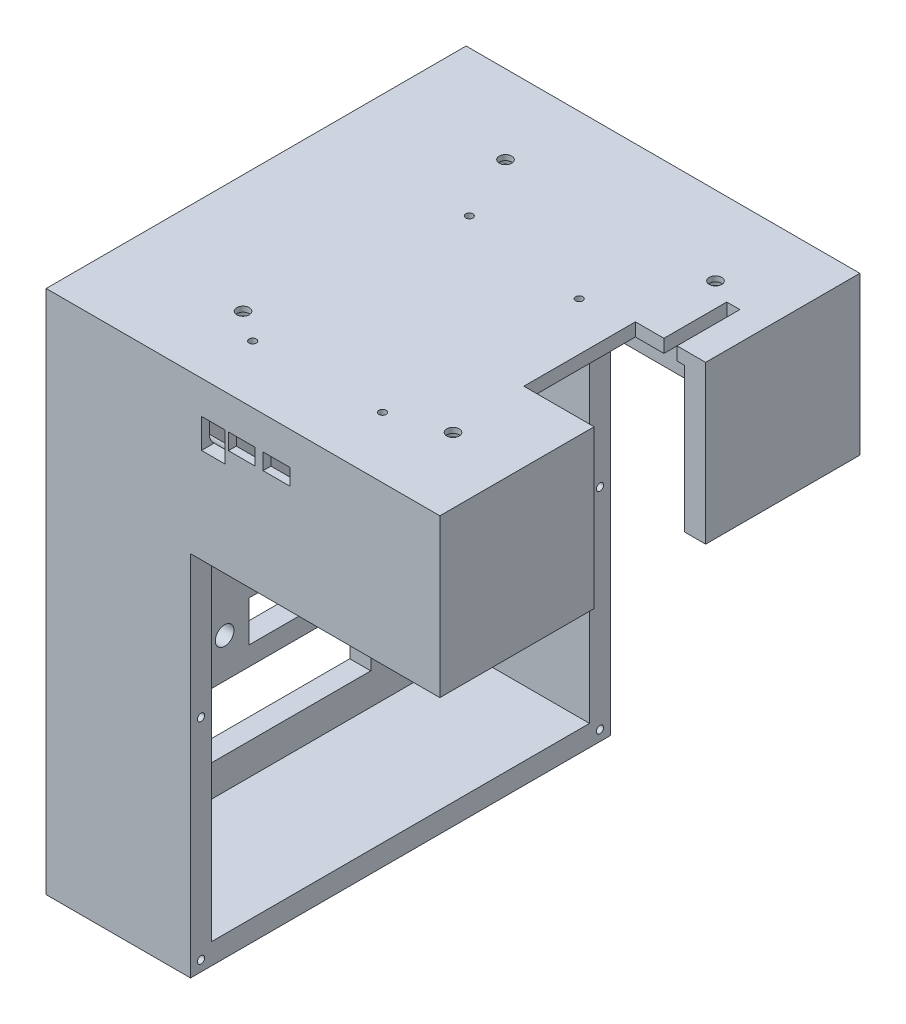
SolidWorks part; units mm, degrees
ref_plane "Front" through (0, 0, 0) normal (0, 0, 1) x (1, 0, 0)
ref_plane "Top" through (0, 0, 0) normal (0, 1, 0) x (1, 0, 0)
ref_plane "Right" through (0, 0, 0) normal (1, 0, 0) x (0, 0, -1)
sketch "Sketch1" plane through (0, 0, 0) normal (0, 1, 0) x (1, 0, 0)
  line L1 (-75, -80) -> (75, -80)
  line L2 (-75, -80) -> (-75, 80)
  line L3 (-75, 80) -> (75, 80)
  line L4 (75, -80) -> (75, 80)
  line L5 (-75, -80) -> (75, 80) construction
  line L6 (-75, 80) -> (75, -80) construction
  point P0 (0, 0)
  dimension "L" = 150
  dimension "W" = 160
extrude "Boss-Extrude1" add sketch "Sketch1" along normal blind 50 and the other way blind 10
sketch "Sketch3" plane through (0, 0, 0) normal (0, 1, 0) x (1, 0, 0)
  line L0 (-75, 80) -> (-75, -80) construction
  line L1 (-67, -72) -> (67, -72)
  line L2 (-67, -72) -> (-67, 72)
  line L3 (-67, 72) -> (67, 72)
  line L4 (67, -72) -> (67, 72)
  line L5 (-67, -72) -> (67, 72) construction
  line L6 (-67, 72) -> (67, -72) construction
  line L7 (75, 80) -> (-75, 80) construction
  point P0 (0, 0)
  dimension "D1" = 8
  dimension "D2" = 8
extrude "Cut-Extrude1" cut sketch "Sketch3" along normal blind 45 and the other way blind 10
ref_plane "Plane1" through (-75, 0, 0) normal (-1, 0, 0) x (0, 0, 1)
sketch "Sketch4" plane through (-75, 0, 0) normal (-1, 0, 0) x (0, 0, 1)
  line L0 (80, 50) -> (80, -10) construction
  line L1 (-80, -10) -> (80, -10)
  line L2 (-80, -10) -> (-80, -150)
  line L3 (-80, -150) -> (80, -150)
  line L4 (80, -10) -> (80, -150)
  dimension "D1" = 140
  dimension "D2" = 0
extrude "Boss-Extrude2" add sketch "Sketch4" against normal blind 55
ref_plane "Plane2" through (-20, 0, 0) normal (1, 0, 0) x (0, 0, -1)
sketch "Sketch7" plane through (-20, 0, 0) normal (1, 0, 0) x (0, 0, -1)
  line L1 (72, -10) -> (-72, -10)
  line L2 (72, -10) -> (72, -142)
  line L3 (72, -142) -> (-72, -142)
  line L4 (-72, -10) -> (-72, -142)
  line L5 (80, -150) -> (-80, -150) construction
  line L6 (-80, -150) -> (-80, -10) construction
  dimension "D1" = 8
  dimension "D2" = 8
extrude "Cut-Extrude3" cut sketch "Sketch7" against normal blind 47
sketch "Sketch12" plane through (-20, 0, 0) normal (1, 0, 0) x (0, 0, -1)
  line L0 (-80, -150) -> (-80, -10) construction
  line L1 (80, -10) -> (80, -150) construction
  line L5 (80, -150) -> (-80, -150) construction
  circle A0 centre (-76, -146) radius 1.375
  circle A1 centre (76, -146) radius 1.375
  circle A2 centre (76, -66) radius 1.375
  circle A3 centre (-76, -66) radius 1.375
  dimension "D1" = 4
  dimension "D2" = 4
  dimension "D4" = 2
  dimension "D5" = 80
  dimension "D6" = 4
  dimension "D7" = 4
  dimension "D9" = 2.75
  dimension "D8" = 4
  dimension "D3" = 2
extrude "Cut-Extrude4" cut sketch "Sketch12" against normal blind 6
ref_plane "Plane3" through (0, -10, 0) normal (0, -1, 0) x (-1, 0, 0)
sketch "Sketch13" plane through (0, -10, 0) normal (0, -1, 0) x (-1, 0, 0)
  line L0 (-75, 80) -> (20, 80) construction
  line L1 (-75, -80) -> (-75, 80) construction
  line L2 (20, -80) -> (-75, -80) construction
  circle A0 centre (-71, 76) radius 1.375
  circle A1 centre (-6, 76) radius 1.375
  circle A2 centre (-6, -76) radius 1.375
  circle A3 centre (-71, -76) radius 1.375
  dimension "D1" = 4
  dimension "D5" = 2.75
  dimension "D2" = 4
  dimension "D3" = 2
  dimension "D6" = 4
  dimension "D7" = 4
  dimension "D8" = 65
  dimension "D4" = 2
extrude "Cut-Extrude5" cut sketch "Sketch13" against normal blind 6
ref_plane "Plane4" through (0, 45, 0) normal (0, -1, 0) x (-1, 0, 0)
sketch "Sketch16" plane through (0, 45, 0) normal (0, -1, 0) x (-1, 0, 0)
  line L0 (67, -72) -> (-67, -72) construction
  circle A0 centre (18.3192, -58) radius 1.375
  circle A1 centre (18.3192, 24.55) radius 1.375
  circle A2 centre (-29.9408, -56.8) radius 1.375
  circle A3 centre (-29.9408, 18.13) radius 1.375
  dimension "D1" = 2
  dimension "D2" = 14
  dimension "D3" = 2
  dimension "D7" = 2.75
  dimension "D8" = 2.75
  dimension "D4" = 48.26
  dimension "D5" = 15.2
  dimension "D6" = 82.55
  dimension "D9" = 74.93
extrude "Cut-Extrude6" cut sketch "Sketch16" against normal blind 6
sketch "Sketch17" plane through (0, 0, 80) normal (0, 0, 1) x (1, 0, 0)
  line L1 (-6.8192, 26.15) -> (-15.8192, 26.15)
  line L2 (-6.8192, 26.15) -> (-6.8192, 37.4)
  line L3 (-6.8192, 37.4) -> (-15.8192, 37.4)
  line L4 (-15.8192, 26.15) -> (-15.8192, 37.4)
  line L5 (-73.7, 45) -> (73.7, 45) construction
  line L7 (17.8308, 37.4) -> (17.8308, 31.2)
  line L8 (-5.5692, 37.4) -> (4.6308, 37.4)
  line L9 (-5.5692, 37.4) -> (-5.5692, 31.2)
  line L10 (-5.5692, 31.2) -> (4.6308, 31.2)
  line L11 (4.6308, 37.4) -> (4.6308, 31.2)
  line L12 (7.6308, 37.4) -> (17.8308, 37.4)
  line L13 (7.6308, 37.4) -> (7.6308, 31.2)
  line L14 (7.6308, 31.2) -> (17.8308, 31.2)
  line L15 (-18.3192, 50) -> (-18.3192, 45) construction
  dimension "D1" = 11.25
  dimension "D2" = 9
  dimension "D3" = 7.6
  dimension "D4" = 2.5
  dimension "D5" = 6.2
  dimension "D6" = 0
  dimension "D7" = 10.2
  dimension "D9" = 1.25
  dimension "D10" = 3
  dimension "D8" = 2
extrude "Cut-Extrude7" cut sketch "Sketch17" against normal blind 5
sketch "Sketch18" plane through (-75, 0, 0) normal (-1, 0, 0) x (0, 0, 1)
  line L0 (-80, -150) -> (80, -150) construction
  line L1 (35.67, -130) -> (-35.67, -130)
  line L2 (35.67, -130) -> (35.67, -105.5)
  line L3 (35.67, -105.5) -> (-35.67, -105.5)
  line L4 (-35.67, -130) -> (-35.67, -105.5)
  line L5 (80, -150) -> (80, 50) construction
  line L7 (10.75, -82.75) -> (-10.75, -82.75)
  line L8 (10.75, -82.75) -> (10.75, -98.25)
  line L9 (10.75, -98.25) -> (-10.75, -98.25)
  line L10 (-10.75, -82.75) -> (-10.75, -98.25)
  line L11 (10.75, -82.75) -> (-10.75, -98.25) construction
  line L12 (10.75, -98.25) -> (-10.75, -82.75) construction
  circle A0 centre (20, -90.5) radius 3.55
  circle A2 centre (-19.791, -90.5) radius 2.6
  circle A4 centre (0, -15) radius 2.35
  point P6 (0, -90.5)
  dimension "D5" = 7.1
  dimension "D9" = 15.5
  dimension "D10" = 5.2
  dimension "D12" = 4.7
  dimension "D15" = 15
  dimension "D1" = 24.5
  dimension "D2" = 71.34
  dimension "D3" = 20
  dimension "D4" = 44.33
  dimension "D6" = 15
  dimension "D7" = 21.5
  dimension "D8" = 15
  dimension "D11" = 15.67
  dimension "D13" = 135
  dimension "D14" = 80
  dimension "D16" = 80
extrude "Cut-Extrude8" cut sketch "Sketch18" against normal blind 15
sketch "Sketch20" plane through (0, 0, 72) normal (0, 0, -1) x (-1, 0, 0)
  line L0 (67, 45) -> (-67, 45) construction
  line L1 (20.8192, 25) -> (-30.8252, 25)
  line L2 (20.8192, 25) -> (20.8192, 40)
  line L3 (20.8192, 40) -> (-30.8252, 40)
  line L4 (-30.8252, 25) -> (-30.8252, 40)
  line L5 (15.8192, 37.4) -> (15.8192, 26.15) construction
  dimension "D1" = 15
  dimension "D2" = 5
  dimension "D3" = 5
extrude "Cut-Extrude9" cut sketch "Sketch20" against normal blind 5
fillet "Fillet3" radius 5 1 edges at (5.003, 25, 77)
sketch "Sketch21" plane through (0, 50, 0) normal (0, 1, 0) x (1, 0, 0)
  line L0 (-20, -80) -> (75, -80) construction
  line L1 (75, 80) -> (-20, 80) construction
  line L2 (75, -80) -> (75, 80) construction
  circle A0 centre (50, 50) radius 2.375
  circle A1 centre (-30, 50) radius 2.375
  circle A2 centre (-30, -50) radius 2.375
  circle A3 centre (50, -50) radius 2.375
  dimension "D3" = 4.75
  dimension "D4" = 30
  dimension "D5" = 30
  dimension "D6" = 25
  dimension "D7" = 80
  dimension "D8" = 100
  dimension "D1" = 2
  dimension "D2" = 2
extrude "Cut-Extrude10" cut sketch "Sketch21" against normal blind 10
sketch "Sketch22" plane through (0, 45, 0) normal (0, -1, 0) x (1, 0, 0)
  line L1 (-67, -72) -> (-67, 72) construction
  line L2 (-20, 72) -> (67, 72) construction
  line L3 (-20, 80) -> (75, 80) construction
  line L4 (75, 80) -> (75, -80) construction
  circle A0 centre (-30, 50) radius 4.95
  circle A1 centre (50, 50) radius 4.95
  circle A2 centre (50, -50) radius 4.95
  circle A3 centre (-30, -50) radius 4.95
  circle A4 centre (-37, 40) radius 1.375
  circle A5 centre (53, 40) radius 1.375
  circle A6 centre (53, -40) radius 1.375
  circle A7 centre (-37, -40) radius 1.375
  dimension "D1" = 9.9
  dimension "D10" = 2.75
  dimension "D11" = 30
  dimension "D6" = 30
  dimension "D7" = 80
  dimension "D8" = 90
  dimension "D9" = 32
  dimension "D12" = 25
  dimension "D13" = 80
  dimension "D2" = 2
  dimension "D3" = 2
  dimension "D4" = 2
  dimension "D5" = 2
extrude "Cut-Extrude11" cut sketch "Sketch22" against normal blind 3
sketch "Sketch23" plane through (-67, 0, 0) normal (1, 0, 0) x (0, 0, -1)
  line L0 (-72, -142) -> (72, -142) construction
  line L1 (72, -142) -> (72, 45) construction
  circle A0 centre (53, -137) radius 1.375
  circle A1 centre (-53, -137) radius 1.375
  circle A2 centre (-53, 3) radius 1.375
  circle A3 centre (53, 3) radius 1.375
  dimension "D8" = 2.75
  dimension "D3" = 5
  dimension "D4" = 19
  dimension "D5" = 106
  dimension "D6" = 5
  dimension "D7" = 140
  dimension "D1" = 2
  dimension "D2" = 2
extrude "Cut-Extrude12" cut sketch "Sketch23" against normal blind 5
sketch "Sketch24" plane through (-75, 0, 0) normal (-1, 0, 0) x (0, 0, 1)
  circle A0 centre (0, -15) radius 60.0382
sketch "Sketch25" plane through (0, -10, 0) normal (0, -1, 0) x (1, 0, 0)
  line L1 (90.75, -21.25) -> (48.25, -21.25)
  line L2 (90.75, -21.25) -> (90.75, 21.25)
  line L3 (90.75, 21.25) -> (48.25, 21.25)
  line L4 (48.25, -21.25) -> (48.25, 21.25)
  line L5 (90.75, -21.25) -> (48.25, 21.25) construction
  line L6 (90.75, 21.25) -> (48.25, -21.25) construction
  point P0 (69.5, 0)
  dimension "D1" = 42.5
  dimension "D2" = 42.5
extrude "Cut-Extrude13" cut sketch "Sketch25" against normal blind 60
sketch "Sketch26" plane through (0, 45, 0) normal (0, -1, 0) x (1, 0, 0)
  line L2 (59.1091, -21.1925) -> (64.1091, -21.1925)
  line L3 (59.1091, -21.1925) -> (59.1091, -45.1925)
  line L4 (59.1091, -45.1925) -> (64.1091, -45.1925)
  line L5 (64.1091, -21.1925) -> (64.1091, -45.1925)
  dimension "D1" = 24
  dimension "D2" = 5
extrude "Cut-Extrude14" cut sketch "Sketch26" against normal blind 5
